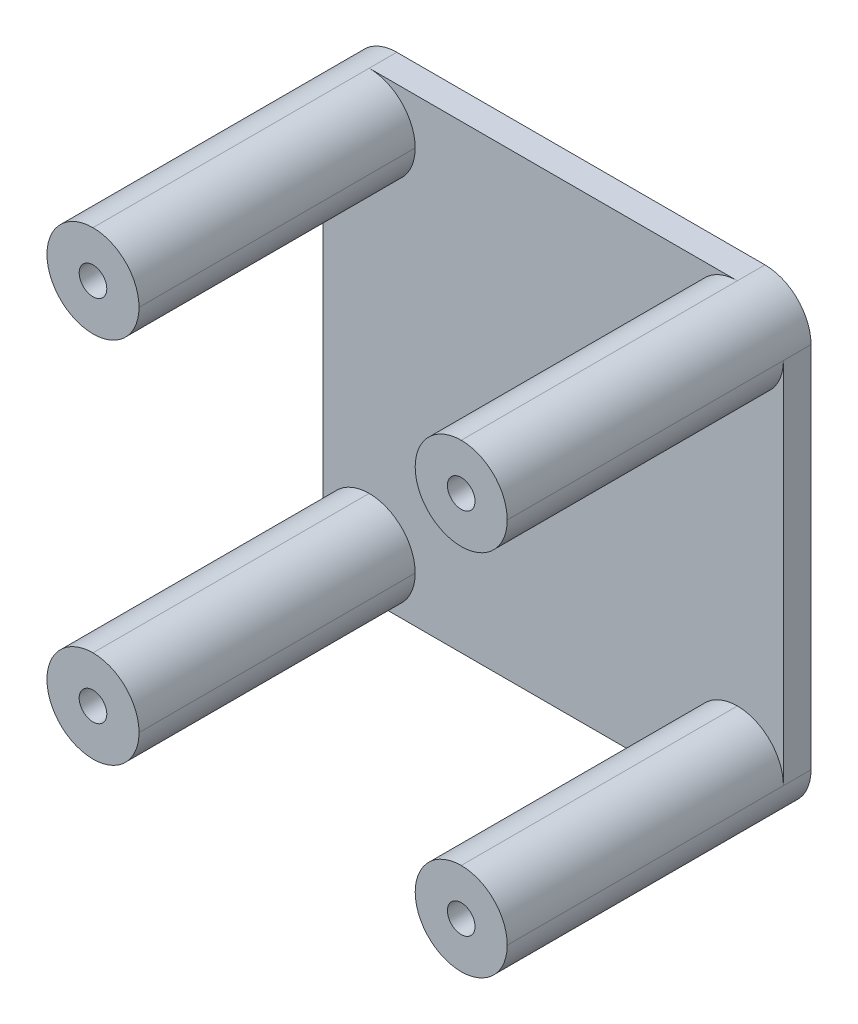
SolidWorks part; units mm, degrees
ref_plane "Front Plane" through (0, 0, 0) normal (0, 0, 1) x (1, 0, 0)
ref_plane "Top Plane" through (0, 0, 0) normal (0, 1, 0) x (1, 0, 0)
ref_plane "Right Plane" through (0, 0, 0) normal (1, 0, 0) x (0, 0, -1)
sketch "Sketch2" plane through (0, 0, 0) normal (0, 0, 1) x (1, 0, 0)
  line L0 (-66.5782, 92.6845) -> (-16.5782, 42.6845) construction
  line L1 (-66.5782, 92.6845) -> (-16.5782, 92.6845)
  line L2 (-66.5782, 92.6845) -> (-66.5782, 42.6845)
  line L3 (-66.5782, 42.6845) -> (-16.5782, 42.6845)
  line L4 (-16.5782, 92.6845) -> (-16.5782, 42.6845)
  line L5 (-61.5782, 87.6845) -> (-21.5782, 87.6845)
  line L6 (-61.5782, 87.6845) -> (-61.5782, 47.6845)
  line L7 (-61.5782, 47.6845) -> (-21.5782, 47.6845)
  line L8 (-21.5782, 87.6845) -> (-21.5782, 47.6845)
  line L9 (-66.5782, 42.6845) -> (-16.5782, 92.6845) construction
  circle A0 centre (-61.5782, 87.6845) radius 1.5
  circle A1 centre (-21.5782, 87.6845) radius 1.5
  circle A2 centre (-61.5782, 47.6845) radius 1.5
  circle A3 centre (-21.5782, 47.6845) radius 1.5
  circle A4 centre (-41.5782, 67.6845) radius 1.25
  dimension "D1" = 50
  dimension "D2" = 50
  dimension "D3" = 5
  dimension "D4" = 5
  dimension "D5" = 5
  dimension "D6" = 5
extrude "Boss-Extrude1" add sketch "Sketch2" along normal blind 3 contours L4 L1 L2 L3 A3 L7 A2 L6 A0 L5 A1 L8 | A3 L8 A1 L5 A0 L6 A2 L7 A4 region at (-41.5782, 91.9774, 0) region at (-41.5782, 87.1188, 0)
sketch "Sketch3" plane through (0, 0, 3) normal (0, 0, 1) x (1, 0, 0)
  line L1 (-66.5782, 92.6845) -> (-56.5782, 92.6845)
  line L2 (-66.5782, 92.6845) -> (-66.5782, 82.6845)
  line L3 (-66.5782, 82.6845) -> (-56.5782, 82.6845)
  line L4 (-56.5782, 92.6845) -> (-56.5782, 82.6845)
  line L5 (-16.5782, 92.6845) -> (-26.5782, 92.6845)
  line L6 (-16.5782, 92.6845) -> (-16.5782, 82.6845)
  line L7 (-16.5782, 82.6845) -> (-26.5782, 82.6845)
  line L8 (-26.5782, 92.6845) -> (-26.5782, 82.6845)
  line L9 (-16.5782, 42.6845) -> (-26.5782, 42.6845)
  line L10 (-16.5782, 42.6845) -> (-16.5782, 52.6845)
  line L11 (-16.5782, 52.6845) -> (-26.5782, 52.6845)
  line L12 (-26.5782, 42.6845) -> (-26.5782, 52.6845)
  line L13 (-66.5782, 42.6845) -> (-56.5782, 42.6845)
  line L14 (-66.5782, 42.6845) -> (-66.5782, 52.6845)
  line L15 (-66.5782, 52.6845) -> (-56.5782, 52.6845)
  line L16 (-56.5782, 42.6845) -> (-56.5782, 52.6845)
  circle A0 centre (-61.5782, 87.6845) radius 1.5
  circle A1 centre (-21.5782, 87.6845) radius 1.5
  circle A2 centre (-21.5782, 47.6845) radius 1.5
  circle A3 centre (-61.5782, 47.6845) radius 1.5
  dimension "D1" = 10
  dimension "D2" = 10
  dimension "D3" = 10
  dimension "D4" = 10
  dimension "D5" = 10
  dimension "D6" = 10
  dimension "D7" = 10
  dimension "D8" = 10
extrude "Boss-Extrude2" add sketch "Sketch3" along normal blind 30
fillet "Fillet2" radius 5 4 edges at (-66.5782, 42.6845, 16.5) (-16.5782, 42.6845, 16.5) (-16.5782, 92.6845, 16.5) (-66.5782, 92.6845, 16.5)
fillet "Fillet3" radius 5 12 edges at (-16.5782, 82.6845, 18) (-26.5782, 82.6845, 18) (-26.5782, 92.6845, 18) (-16.5782, 52.6845, 18) (-26.5782, 52.6845, 18) (-26.5782, 42.6845, 18) (-56.5782, 42.6845, 18) (-56.5782, 52.6845, 18) (-66.5782, 52.6845, 18) (-66.5782, 82.6845, 18) (-56.5782, 82.6845, 18) (-56.5782, 92.6845, 18)
